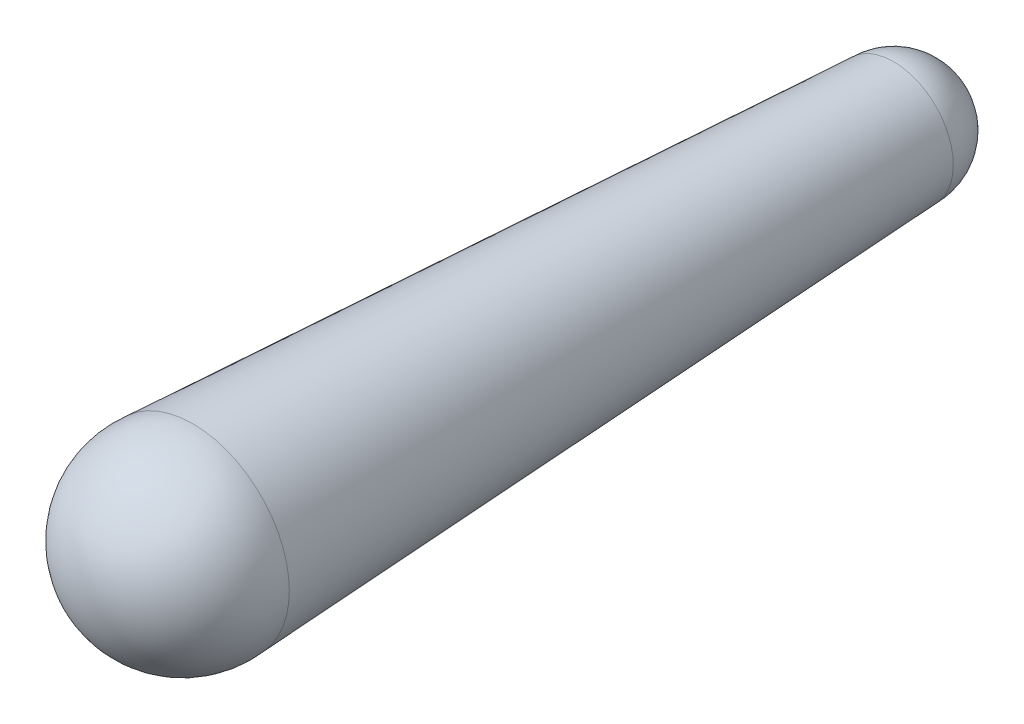
SolidWorks part; units mm, degrees
ref_plane "Front Plane" through (0, 0, 0) normal (0, 0, 1) x (1, 0, 0)
ref_plane "Top Plane" through (0, 0, 0) normal (0, 1, 0) x (1, 0, 0)
ref_plane "Right Plane" through (0, 0, 0) normal (1, 0, 0) x (0, 0, -1)
sketch "Sketch1" plane through (0, 0, 0) normal (0, 0, 1) x (1, 0, 0)
  circle A0 centre (0, 0) radius 57.15
  dimension "D1" = 114.3
extrude "Boss-Extrude1" add sketch "Sketch1" against normal blind 419.1 draft 3
sketch "Sketch2" plane through (0, 0, 0) normal (0, 0, 1) x (1, 0, 0)
  point P0 (0, 0)
sketch "Sketch3" plane through (0, 0, -419.1) normal (0, 0, -1) x (-1, 0, 0)
  point P0 (0, 0)
sketch3d "3DSketch1"
  line L0 (0, 0, 0) -> (0, 0, -419.1)
sketch "Sketch4" plane through (0, 0, 0) normal (1, 0, 0) x (0, 0, -1)
  line L0 (419.1, -35.1859) -> (419.1, 35.1859) construction
  line L1 (419.1, 35.1859) -> (419.1, -35.1859)
  arc A0 (419.1, 35.1859) -> (419.1, -35.1859) centre (419.1, 0) cw
revolve "Revolve1" add sketch "Sketch4" angle 360 about L1
sketch "Sketch5" plane through (0, 0, 0) normal (1, 0, 0) x (0, 0, -1)
  line L0 (0, 57.15) -> (0, -57.15) construction
  line L1 (0, 57.15) -> (0, -57.15)
  arc A0 (0, 57.15) -> (0, -57.15) centre (0, 0) ccw
revolve "Revolve2" add sketch "Sketch5" angle 360 about L1
